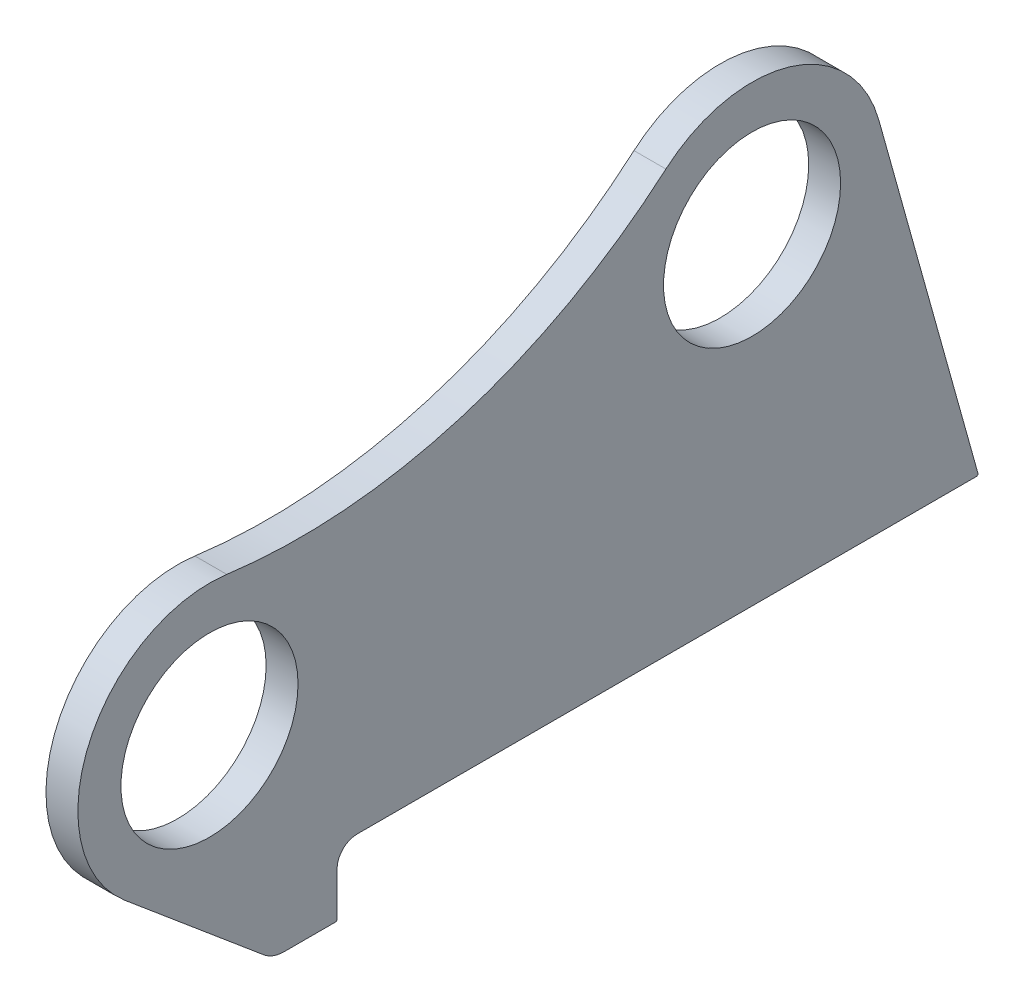
SolidWorks part; units mm, degrees
material "MS-Grade 350"
ref_plane "Front Plane" through (0, 0, 0) normal (0, 0, 1) x (1, 0, 0)
ref_plane "Top Plane" through (0, 0, 0) normal (0, 1, 0) x (1, 0, 0)
ref_plane "Right Plane" through (0, 0, 0) normal (1, 0, 0) x (0, 0, -1)
sketch "Sketch1" plane through (0, 0, 0) normal (1, 0, 0) x (0, 0, -1)
  line L0 (0, -41) -> (0, -12.5)
  line L1 (12.5, 0) -> (402, 0)
  line L3 (402, 0) -> (339.5406, 224.0212)
  line L4 (-133.0582, 36.825) -> (-45.9722, -36.3151)
  line L11 (0, -41) -> (-33.1096, -41)
  line L12 (-80, 100) -> (260.0715, 201.8644) construction
  circle A0 centre (-80, 100) radius 55.5
  circle A1 centre (260.0715, 201.8644) radius 55.5
  arc A2 (-69.1527, 181.7838) -> (-133.0582, 36.825) centre (-80, 100) ccw
  arc A4 (-45.9722, -36.3151) -> (-33.1096, -41) centre (-33.1096, -21) ccw
  arc A5 (0, -12.5) -> (12.5, 0) centre (12.5, -12.5) cw
  arc A9 (339.5406, 224.0212) -> (206.0497, 264.2174) centre (260.0715, 201.8644) ccw
  arc A10 (-69.1527, 181.7838) -> (206.0497, 264.2174) centre (-23.1337, 528.7452) ccw
  point P31 (0, 0)
  dimension "D2" = 100
  dimension "D4" = 82.5
  dimension "D5" = 111
  dimension "D6" = 41
  dimension "D7" = 350
  dimension "D13" = 40.026
  dimension "D20" = 12.5
  dimension "D3" = 20
  dimension "D12" = 402
  dimension "D15" = 16.675
  dimension "D16" = 355
  dimension "D17" = 80
sheet metal parameters "Sheet-Metal1" thickness 20 parameters "D1"=92
base flange "Base-Flange1" sketch "Sketch1" thickness 20 reverse thickness direction no parameters "D1"=92
fillet "Fillet-1.0" radius 1 2 edges at (-10, 0, -402) (-10, -41, 0)
flat pattern "Flat-Pattern1" [suppressed]
sketch "Bend-Lines1" plane through (0, 0, 0) normal (0, 1, 0) x (1, 0, 0)
sketch3d "Bounding-Box1" [suppressed]
  line L0 (-159.6299, -579.154, 0) -> (414.8787, -520.584, 0) construction
  line L1 (-191.1408, -270.0661, 0) -> (383.3678, -211.4961, 0) construction
  line L2 (-159.6299, -579.154, 0) -> (-191.1408, -270.0661, 0) construction
  line L3 (414.8787, -520.584, 0) -> (383.3678, -211.4961, 0) construction
